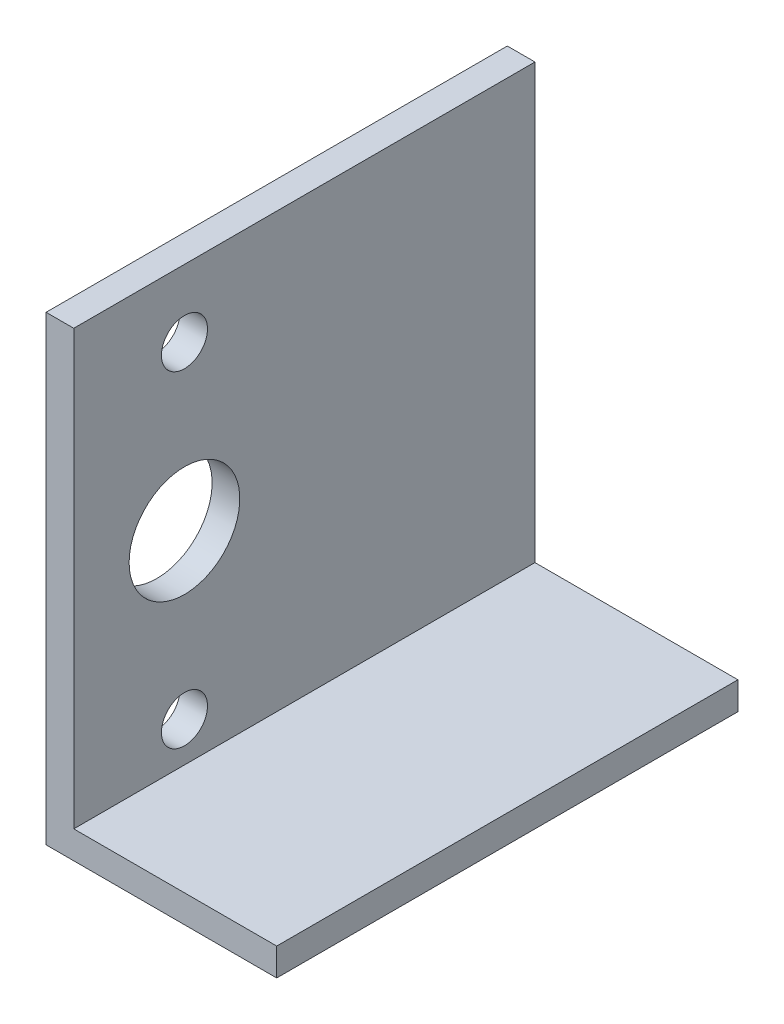
SolidWorks part; units mm, degrees
ref_plane "Alzado" through (0, 0, 0) normal (0, 0, 1) x (1, 0, 0)
ref_plane "Planta" through (0, 0, 0) normal (0, 1, 0) x (1, 0, 0)
ref_plane "Vista lateral" through (0, 0, 0) normal (1, 0, 0) x (0, 0, -1)
sketch "Croquis1" plane through (0, 0, 0) normal (0, 0, 1) x (1, 0, 0)
  line L0 (0, 50) -> (0, 0)
  line L1 (0, 0) -> (25, 0)
  line L2 (3, 50) -> (3, 3)
  line L3 (3, 3) -> (25, 3)
  line L4 (0, 50) -> (3, 50)
  line L5 (25, 0) -> (25, 3)
  dimension "D1" = 50
  dimension "D2" = 25
  dimension "D3" = 3
extrude "Saliente-Extruir1" add sketch "Croquis1" along normal blind 50
sketch "Croquis2" plane through (0, 0, 0) normal (-1, 0, 0) x (0, 0, 1)
  line L0 (38, 50) -> (38, 0) construction
  line L1 (50, 50) -> (0, 50) construction
  line L2 (50, 0) -> (0, 0) construction
  line L3 (50, 50) -> (50, 0) construction
  line L4 (0, 25) -> (50, 25) construction
  line L5 (0, 50) -> (0, 0) construction
  circle A0 centre (38, 25) radius 6
  circle A1 centre (38, 42.7) radius 2.5
  circle A2 centre (38, 7.3) radius 2.5
  dimension "D3" = 12
  dimension "D6" = 5
  dimension "D1" = 12
  dimension "D2" = 25
  dimension "D4" = 35.4
  dimension "D5" = 17.7
extrude "Cortar-Extruir1" cut sketch "Croquis2" against normal up to surface (3 mm away) up to face at (3, 26.5, 25)
equation "\"D5@Croquis2\"=\"D4@Croquis2\"/2"
